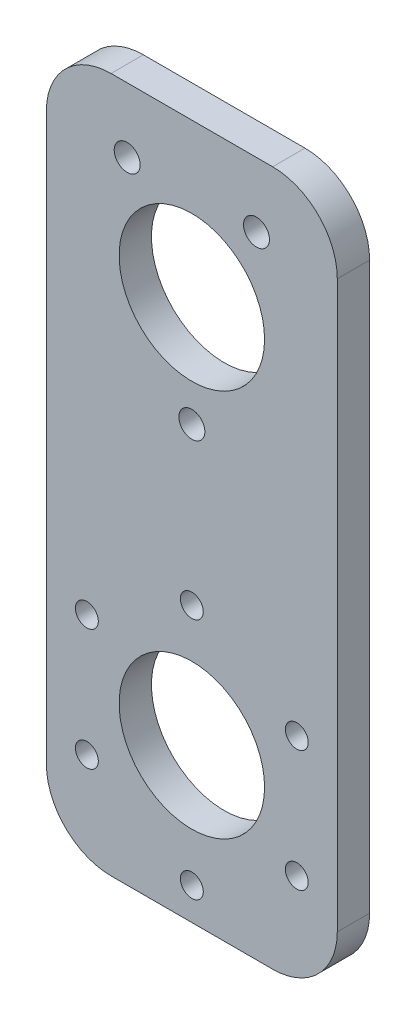
SolidWorks part; units mm, degrees
material "6061-T6 (SS)"
ref_plane "Front Plane" through (0, 0, 0) normal (0, 0, 1) x (1, 0, 0)
ref_plane "Top Plane" through (0, 0, 0) normal (0, 1, 0) x (1, 0, 0)
ref_plane "Right Plane" through (0, 0, 0) normal (1, 0, 0) x (0, 0, -1)
sketch "Sketch1" plane through (0, 0, 0) normal (0, 0, 1) x (1, 0, 0)
  line L0 (0, -38.1) -> (0, 38.1) construction
  line L2 (-28.575, 68.2625) -> (28.575, 68.2625)
  line L3 (-28.575, 68.2625) -> (-28.575, -68.2625)
  line L4 (-28.575, -68.2625) -> (28.575, -68.2625)
  line L5 (28.575, 68.2625) -> (28.575, -68.2625)
  line L6 (-28.575, 68.2625) -> (28.575, -68.2625) construction
  line L7 (-28.575, -68.2625) -> (28.575, 68.2625) construction
  circle A0 centre (0, 38.1) radius 14.2875
  circle A1 centre (0, -38.1) radius 14.2875
  point P7 (0, 0)
  point P18 (0, -38.1)
  dimension "D1" = 28.575
  dimension "D2" = 76.2
  dimension "D6" = 136.525
  dimension "D7" = 57.15
extrude "Boss-Extrude1" add sketch "Sketch1" along normal mid plane 6.35
fillet "Fillet1" radius 12.7 4 edges at (28.575, -68.2625, 0) (-28.575, -68.2625, 0) (-28.575, 68.2625, 0) (28.575, 68.2625, 0)
hole_wizard "#8 Clearance Hole1" positions "Sketch3" profile "Sketch2" hole size "#8" standard "ANSI Inch" end condition through all
sketch "Sketch3" plane through (0, 0, 3.175) normal (0, 0, 1) x (1, 0, 0)
  circle A0 centre (0, -38.1) radius 14.2875 construction
  point P0 (0, -14.2875)
  point P10 (20.6222, -26.1937)
  point P11 (20.6222, -50.0062)
  point P12 (0, -61.9125)
  point P13 (-20.6222, -50.0063)
  point P14 (-20.6222, -26.1938)
  point P15 (0, -38.1)
  dimension "D1" = 23.8125
  dimension "D2" = 6
sketch "Sketch2" plane through (0, -14.2875, 3.175) normal (1, 0, 0) x (0, -1, 0)
  line L0 (0, 0) -> (0, 6.35)
  line L1 (0, 6.35) -> (2.2479, 6.35)
  line L2 (2.2479, 6.35) -> (2.2479, 0)
  line L5 (2.2479, 0) -> (0, 0)
  line L11 (0, -6.35) -> (0, 107.95) construction
  dimension "Thru Hole Dia." = 4.4958
  dimension "Thru Hole Depth" = 6.35
hole_wizard "#10 Clearance Hole1" positions "Sketch7" profile "Sketch5" hole size "#10" standard "ANSI Inch" end condition through all
sketch "Sketch7" plane through (0, 0, 3.175) normal (0, 0, 1) x (1, 0, 0)
  line L0 (-12.7, 55.5625) -> (12.7, 55.5625) construction
  line L2 (15.875, 68.2625) -> (-15.875, 68.2625) construction
  circle A3 centre (0, 38.1) radius 15.875
  circle A4 centre (0, 38.1) radius 15.875 construction
  circle A5 centre (-12.7, 55.5625) radius 7.9375 construction
  circle A8 centre (0, 16.51) radius 7.9375 construction
  point P0 (-12.7, 55.5625)
  point P2 (12.7, 55.5625)
  point P9 (0, 55.5625)
  point P29 (0, 16.51)
  dimension "D4" = 15.875
  dimension "D1" = 25.4
  dimension "D2" = 12.7
  dimension "D5" = 21.59
  dimension "D3" = 1.5875
sketch "Sketch5" plane through (-12.7, 55.5625, 3.175) normal (1, 0, 0) x (0, -1, 0)
  line L0 (0, 0) -> (0, 6.35)
  line L1 (0, 6.35) -> (2.5527, 6.35)
  line L2 (2.5527, 6.35) -> (2.5527, 0)
  line L5 (2.5527, 0) -> (0, 0)
  line L11 (0, -6.35) -> (0, 107.95) construction
  dimension "Thru Hole Dia." = 5.1054
  dimension "Thru Hole Depth" = 6.35
